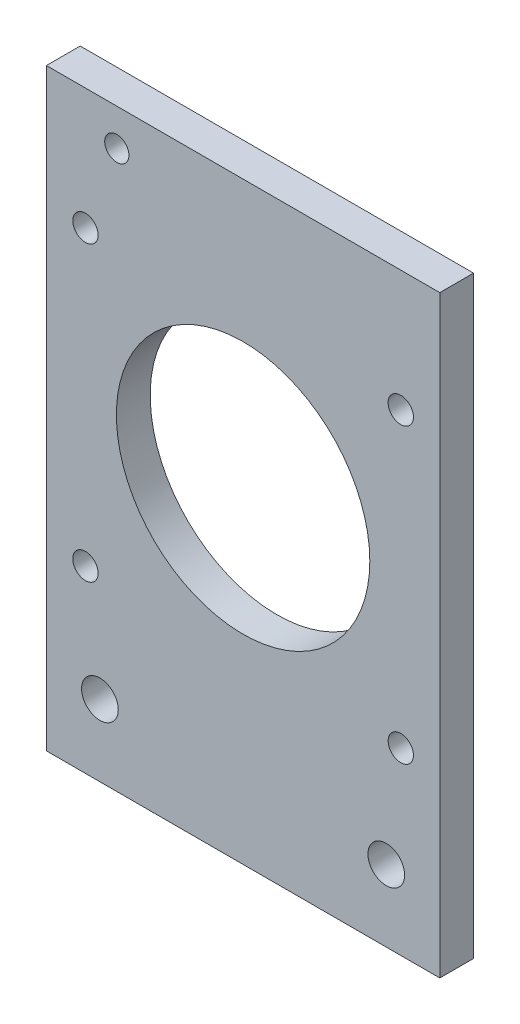
SolidWorks part; units mm, degrees
ref_plane "Front Plane" through (0, 0, 0) normal (0, 0, 1) x (1, 0, 0)
ref_plane "Top Plane" through (0, 0, 0) normal (0, 1, 0) x (1, 0, 0)
ref_plane "Right Plane" through (0, 0, 0) normal (1, 0, 0) x (0, 0, -1)
sketch "Sketch2" plane through (0, 0, 0) normal (0, 0, 1) x (1, 0, 0)
  line L0 (-55, 48.4) -> (55, 48.4) construction
  line L1 (-34.925, 0) -> (34.925, 0)
  line L2 (-34.925, 0) -> (-34.925, 57.9)
  line L3 (-34.925, 57.9) -> (34.925, 57.9) construction
  line L4 (34.925, 0) -> (34.925, 57.9)
  line L5 (0, 48.4) -> (0, 0) construction
  line L6 (0, 48.4) -> (0, 57.9) construction
  line L7 (-34.925, 25.4) -> (34.925, 25.4) construction
  line L10 (34.925, 90.4) -> (-34.925, 90.4) construction
  line L11 (34.925, 57.9) -> (34.925, 90.4)
  line L12 (34.925, 90.4) -> (-34.925, 90.4) construction
  line L13 (-34.925, 90.4) -> (-34.925, 57.9)
  line L14 (34.925, 90.4) -> (34.925, 105.4)
  line L15 (34.925, 105.4) -> (-34.925, 105.4)
  line L16 (-34.925, 90.4) -> (-34.925, 105.4)
  line L17 (-34.925, 25.4) -> (34.925, 25.4) construction
  circle A0 centre (-55, 48.4) radius 3 construction
  circle A1 centre (55, 48.4) radius 3 construction
  circle A2 centre (-55, 48.4) radius 15 construction
  circle A3 centre (55, 48.4) radius 15 construction
  circle A6 centre (0, 57.9) radius 22.5
  circle A7 centre (-55, 48.4) radius 15.6 construction
  point P6 (0, 0)
  dimension "D1" = 6
  dimension "D2" = 30
  dimension "D5" = 45
  dimension "D9" = 15
  dimension "D3" = 110
  dimension "D4" = 9.5
  dimension "D6" = 69.85
  dimension "D7" = 0.6
  dimension "D8" = 32.5
  dimension "D10" = 25.4
  dimension "D12" = 32.5
extrude "Boss-Extrude1" add sketch "Sketch2" along normal mid plane 6
sketch "Sketch3" plane through (0, 0, 3) normal (0, 0, 1) x (1, 0, 0)
  line L0 (34.925, 105.4) -> (-34.925, 105.4) construction
  line L1 (-34.925, 0) -> (-25.425, 0) construction
  line L2 (-34.925, 0) -> (-34.925, 12.7) construction
  line L3 (-34.925, 12.7) -> (-25.425, 12.7) construction
  line L4 (-25.425, 0) -> (-25.425, 12.7) construction
  line L5 (34.925, 0) -> (25.425, 0) construction
  line L6 (34.925, 0) -> (34.925, 12.7) construction
  line L7 (34.925, 12.7) -> (25.425, 12.7) construction
  line L8 (25.425, 0) -> (25.425, 12.7) construction
  line L11 (-34.925, 105.4) -> (-34.925, 0) construction
  circle A0 centre (-25.425, 12.7) radius 3.2576
  circle A1 centre (25.425, 12.7) radius 3.2576
  circle A4 centre (-22.425, 98.9) radius 2.15
  dimension "D1" = 12.7
  dimension "D2" = 6.5151
  dimension "D7" = 4.3
  dimension "D3" = 9.5
  dimension "D8" = 12.5
  dimension "D9" = 6.5
extrude "Cut-Extrude1" cut sketch "Sketch3" against normal blind 6
sketch "Sketch4" plane through (0, 0, 3) normal (0, 0, 1) x (1, 0, 0)
  circle A0 centre (-28, 31.9) radius 2.25 construction
  circle A1 centre (28, 83.9) radius 2.25 construction
  circle A2 centre (-28, 83.9) radius 2.25 construction
  circle A3 centre (-28, 31.9) radius 2.25
  circle A4 centre (28, 83.9) radius 2.25
  circle A5 centre (-28, 83.9) radius 2.25
  circle A6 centre (28, 31.9) radius 2.25
  point P11 (0, 0)
  point P13 (0, 0)
extrude "Cut-Extrude2" cut sketch "Sketch4" against normal blind 10
